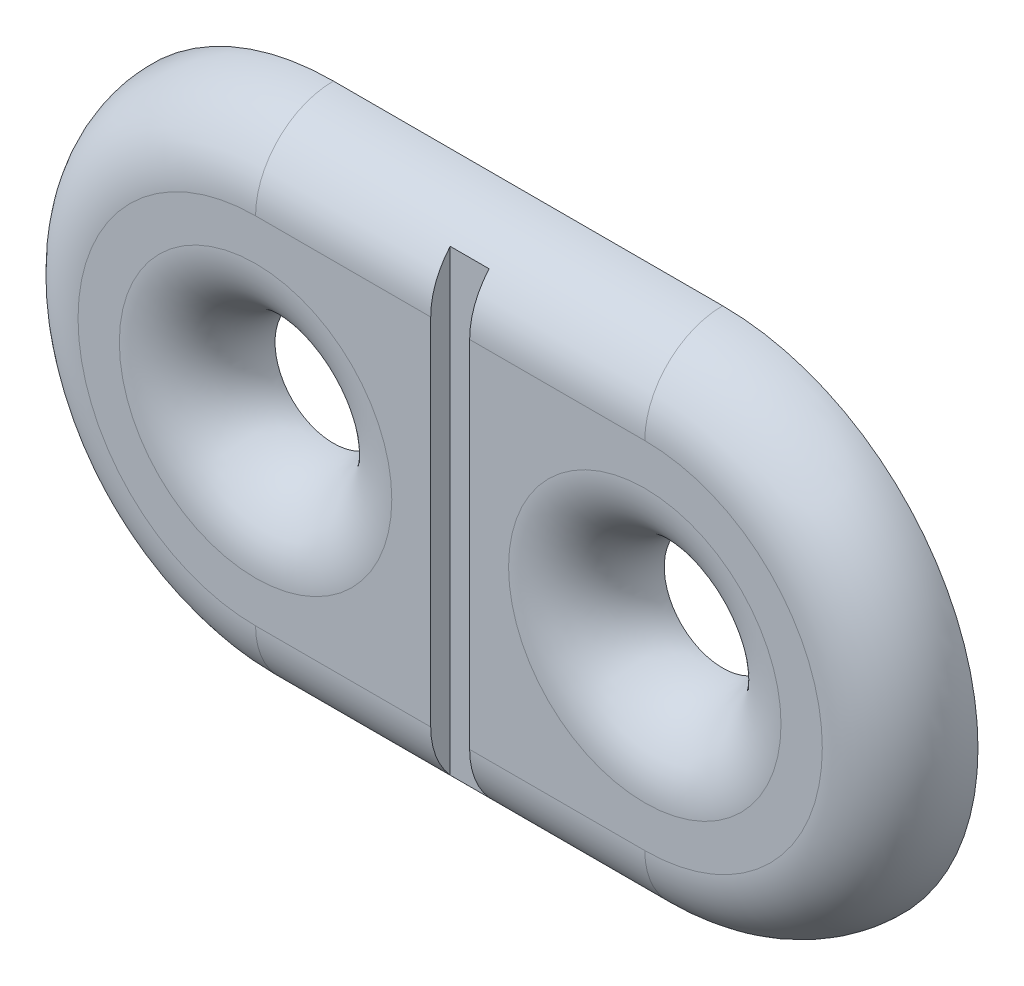
SolidWorks part; units mm, degrees
ref_plane "前视基准面" through (0, 0, 0) normal (0, 0, 1) x (1, 0, 0)
ref_plane "上视基准面" through (0, 0, 0) normal (0, 1, 0) x (1, 0, 0)
ref_plane "右视基准面" through (0, 0, 0) normal (1, 0, 0) x (0, 0, -1)
sketch "草图1" plane through (0, 0, 0) normal (0, 0, 1) x (1, 0, 0)
  line L0 (0, 0) -> (10, 0) construction
  line L1 (0, 6.5607) -> (10, 6.5607)
  line L2 (0, -6.5607) -> (10, -6.5607)
  arc A0 (0, 6.5607) -> (0, -6.5607) centre (0, 0) ccw
  arc A1 (10, -6.5607) -> (10, 6.5607) centre (10, 0) ccw
  circle A2 centre (0, 0) radius 1.5
  circle A3 centre (10, 0) radius 1.5
  point P2 (5, 0)
  dimension "D1" = 3
  dimension "D2" = 3
  dimension "D4" = 6.5607
  dimension "D3" = 10
extrude "凸台-拉伸1" add sketch "草图1" along normal blind 2
fillet "圆角1" radius 2 6 edges at (11.5, 0, 2) (5, 6.5607, 2) (16.5607, 0, 2) (5, -6.5607, 2) (-6.5607, 0, 2) (1.5, 0, 2)
sketch "草图2" plane through (0, 0, 0) normal (0, 1, 0) x (1, 0, 0)
  line L0 (10, -2) -> (0, -2) construction
  line L1 (4.5, -2.5) -> (5.5, -2.5)
  line L2 (4.5, -2.5) -> (4.5, -1.5)
  line L3 (4.5, -1.5) -> (5.5, -1.5)
  line L4 (5.5, -2.5) -> (5.5, -1.5)
  line L5 (4.5, -2.5) -> (5.5, -1.5) construction
  line L6 (4.5, -1.5) -> (5.5, -2.5) construction
  point P0 (5, -2)
  dimension "D1" = 1
  dimension "D2" = 1
extrude "切除-拉伸1" cut sketch "草图2" against normal mid plane 100
